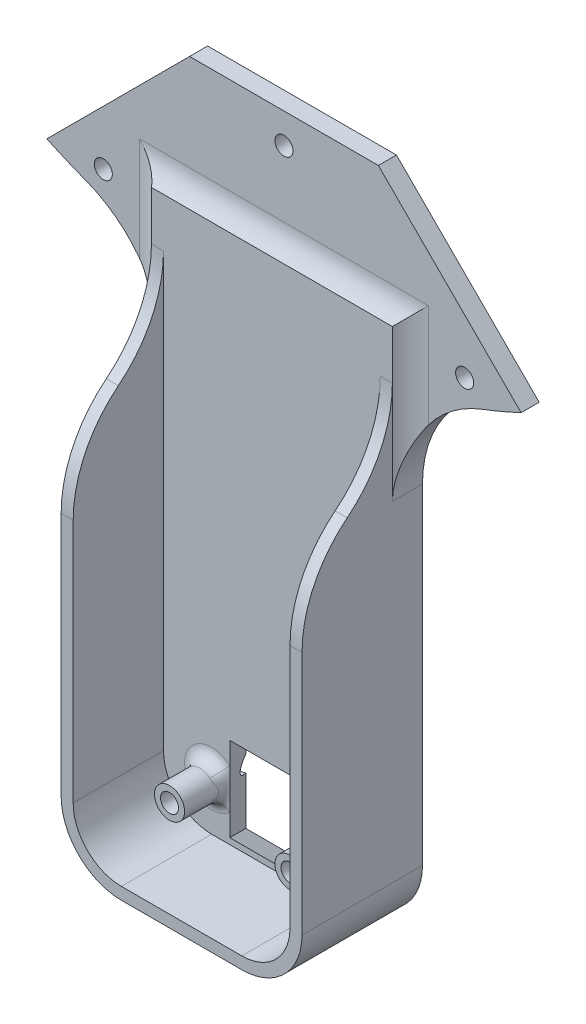
SolidWorks part; units mm, degrees
ref_plane "Alzado" through (0, 0, 0) normal (0, 0, 1) x (1, 0, 0)
ref_plane "Planta" through (0, 0, 0) normal (0, 1, 0) x (1, 0, 0)
ref_plane "Vista lateral" through (0, 0, 0) normal (1, 0, 0) x (0, 0, -1)
sketch "Croquis1" plane through (0, 0, 0) normal (0, 0, 1) x (1, 0, 0)
  line L0 (15.6764, -60) -> (-15.6764, -60)
  line L1 (-15.6764, -60) -> (-39.3766, -83.7002)
  line L2 (15.6764, -60) -> (39.3766, -83.7002)
  circle A3 centre (-30, -83.3725) radius 1.5
  circle A4 centre (30, -83.3725) radius 1.5
  circle A5 centre (0, -65) radius 1.5
  circle A6 centre (0, 0) radius 88.6057 construction
  arc A7 (-39.3766, -83.7002) -> (39.3766, -83.7002) centre (0, 0) ccw
  point P13 (0, -60)
  dimension "D4" = 177.2115
  dimension "D5" = 3
  dimension "D9" = 185
  dimension "D1" = 65
  dimension "D2" = 30
  dimension "D3" = 30
  dimension "D6" = 5
  dimension "D7" = 45
  dimension "D8" = 45
extrude "Saliente-Extruir1" add sketch "Croquis1" along normal blind 3
sketch "Croquis2" plane through (0, 0, 3) normal (0, 0, 1) x (1, 0, 0)
  line L0 (-1.4473, -80) -> (20, -80)
  line L1 (20, -80) -> (20, -160)
  line L2 (10, -170) -> (-10, -170)
  line L3 (-20, -160) -> (-20, -80)
  line L4 (-20, -80) -> (-1.4473, -80)
  line L5 (15.6764, -60) -> (-15.6764, -60) construction
  line L6 (0, -170) -> (0, -80) construction
  line L7 (10, -160) -> (-10, -160) construction
  line L9 (7, -153) -> (-7, -153)
  line L10 (7, -153) -> (7, -167)
  line L11 (7, -167) -> (-7, -167)
  line L12 (-7, -153) -> (-7, -167)
  line L13 (7, -153) -> (-7, -167) construction
  line L14 (7, -167) -> (-7, -153) construction
  arc A0 (-10, -170) -> (-20, -160) centre (-10, -160) cw
  arc A1 (20, -160) -> (10, -170) centre (10, -160) cw
  circle A2 centre (-10, -160) radius 1.5
  circle A3 centre (10, -160) radius 1.5
  point P7 (0, -60)
  point P8 (0, -170)
  point P11 (-20, -170)
  point P14 (20, -170)
  point P21 (0, -160)
  point P23 (0, -160)
  dimension "D4" = 10
  dimension "D6" = 3
  dimension "D1" = 40
  dimension "D2" = 90
  dimension "D3" = 20
  dimension "D5" = 20
  dimension "D7" = 14
  dimension "D8" = 14
extrude "Saliente-Extruir2" add sketch "Croquis2" along normal blind 2 and the other way up to surface (3 mm away) other way up to face at (0, -74.0501, 0)
fillet "Redondeo1" radius 5 3 edges at (-20, -85.156, 3) (20, -85.156, 3) (0, -80, 3)
sketch "Croquis3" plane through (0, 0, 5) normal (0, 0, 1) x (1, 0, 0)
  circle A0 centre (-10, -160) radius 2.5
  circle A1 centre (-10, -160) radius 1.5
  circle A2 centre (10, -160) radius 1.5
  circle A3 centre (10, -160) radius 2.5
  dimension "D1" = 5
extrude "Saliente-Extruir3" add sketch "Croquis3" along normal blind 7
chamfer "Chaflán1" distance 5 angle 25 4 edges at (-7, -160, 0) (0, -167, 0) (7, -160, 0) (0, -153, 0) first distance on face at (-7, -160, 2.5) first distance on face at (0, -167, 2.5) first distance on face at (7, -160, 2.5) first distance on face at (0, -153, 2.5)
fillet "Redondeo2" radius 20 2 edges at (-20, -90.312, 2.5) (20, -90.312, 2.5)
sketch "Croquis4" plane through (0, 0, 5) normal (0, 0, 1) x (1, 0, 0)
  line L0 (-10, -170) -> (10, -170) construction
  line L1 (-10, -170) -> (10, -170)
  line L2 (-10, -168) -> (10, -168)
  line L3 (-20, -160) -> (-20, -107.5086)
  line L5 (-20, -107.5086) -> (-18, -107.5086)
  line L6 (-18, -107.5086) -> (-18, -160)
  line L7 (18, -160) -> (18, -107.5086)
  line L8 (18, -107.5086) -> (20, -107.5086)
  line L10 (20, -107.5086) -> (20, -160)
  arc A0 (10, -170) -> (20, -160) centre (10, -160) ccw construction
  arc A1 (-20, -160) -> (-10, -170) centre (-10, -160) ccw construction
  arc A2 (10, -170) -> (20, -160) centre (10, -160) ccw
  arc A3 (-20, -160) -> (-10, -170) centre (-10, -160) ccw
  arc A4 (-18, -160) -> (-10, -168) centre (-10, -160) ccw
  arc A5 (10, -168) -> (18, -160) centre (10, -160) ccw
  point P12 (0, 0)
  dimension "D1" = 2
extrude "Saliente-Extruir4" add sketch "Croquis4" along normal blind 15
fillet "Redondeo3" radius 20 2 edges at (19, -107.5086, 5) (-19, -107.5086, 5)
fillet "Redondeo4" radius 20 2 edges at (-19, -107.5086, 20) (19, -107.5086, 20)
fillet "Redondeo5" radius 2 2 edges at (7.5, -160, 5) (-12.5, -160, 5)
